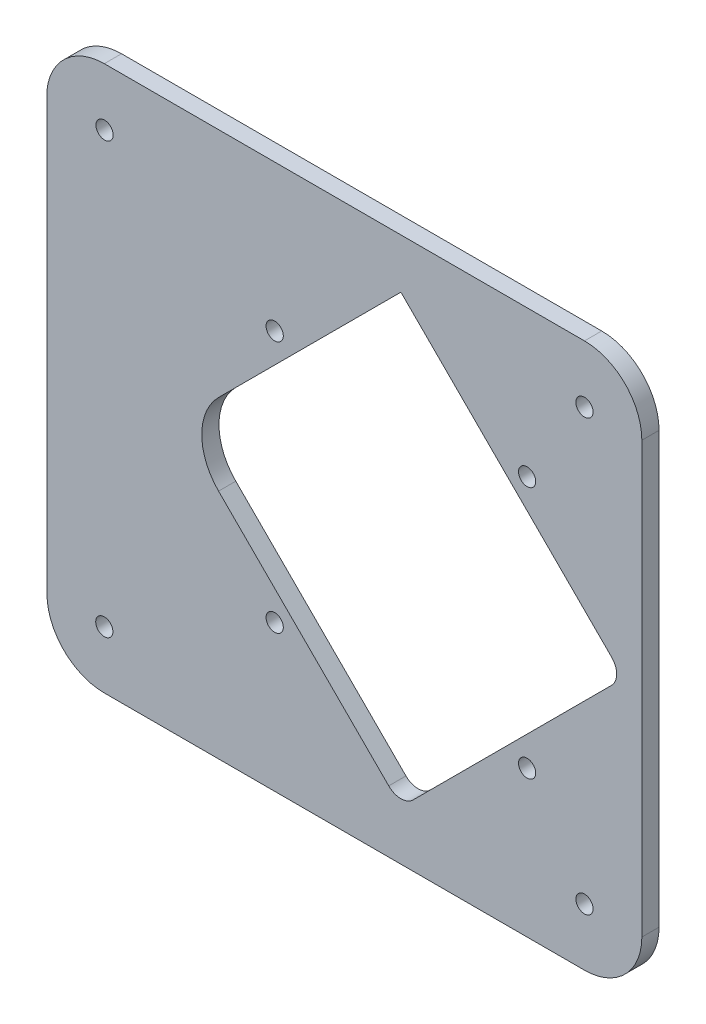
SolidWorks part; units mm, degrees
ref_plane "Front Plane" through (0, 0, 0) normal (0, 0, 1) x (1, 0, 0)
ref_plane "Top Plane" through (0, 0, 0) normal (0, 1, 0) x (1, 0, 0)
ref_plane "Right Plane" through (0, 0, 0) normal (1, 0, 0) x (0, 0, -1)
sketch "Model" plane through (0, 0, 0) normal (0, 0, 1) x (1, 0, 0)
  line L0 (75.7359, 67.6401) -> (82.0642, 73.9684)
  line L3 (117.2673, 85.8158) -> (33.5676, 85.8158)
  line L4 (23.5676, 11.7907) -> (23.5676, 67.2113)
  line L5 (23.5676, 0.8161) -> (23.5676, 11.7907)
  line L6 (23.5676, 67.2113) -> (23.5676, 76.8159)
  line L7 (127.2672, 11.5942) -> (127.2672, 49.316)
  line L8 (127.2672, 49.316) -> (127.2672, 75.8159)
  line L9 (127.2672, 0.8161) -> (127.2672, 11.5942)
  line L10 (33.5676, -9.1838) -> (117.2673, -9.1838)
  line L11 (63.2676, 16.3159) -> (107.2676, 16.3159) construction
  line L12 (107.2676, 60.3158) -> (107.2676, 16.3159) construction
  line L22 (122.0014, 40.4377) -> (89.4636, 72.9755)
  line L23 (87.3887, 1.5824) -> (122.0014, 36.1951)
  line L24 (53.4833, 31.2453) -> (83.1461, 1.5824)
  line L25 (85.2674, 77.1716) -> (82.0642, 73.9684)
  line L26 (89.4636, 72.9755) -> (85.2674, 77.1716)
  line L27 (75.7359, 67.6401) -> (53.3954, 45.2995)
  circle A0 centre (63.2676, 16.3159) radius 1.5
  circle A1 centre (117.2672, 75.8159) radius 1.5
  circle A2 centre (117.2672, 0.8161) radius 1.5
  circle A3 centre (33.61, 75.8159) radius 1.5
  circle A4 centre (33.5676, 0.8161) radius 1.5
  circle A5 centre (107.2676, 16.3159) radius 1.5
  circle A6 centre (63.2676, 60.3159) radius 1.5
  circle A7 centre (107.2676, 60.3158) radius 1.5
  arc A8 (127.2672, 75.8159) -> (117.2673, 85.8158) centre (117.2673, 75.816) ccw
  arc A9 (117.2673, -9.1838) -> (127.2672, 0.8161) centre (117.2672, 0.8161) ccw
  arc A10 (23.5676, 0.8161) -> (33.5676, -9.1838) centre (33.5676, 0.8162) ccw
  arc A11 (33.5676, 85.8158) -> (23.5676, 76.8159) centre (33.6101, 75.7131) ccw
  arc A12 (122.0014, 36.1951) -> (122.0014, 40.4377) centre (119.8801, 38.3164) ccw
  arc A13 (83.1461, 1.5824) -> (87.3887, 1.5824) centre (85.2674, 3.7037) ccw
  arc A14 (53.4833, 45.3874) -> (53.4833, 31.2453) centre (60.5543, 38.3164) ccw
  dimension "D1" = 44
  dimension "D2" = 44
extrude "Boss-Extrude1" add sketch "Model" along normal blind 3 contours A11 L6 L4 L5 A10 L10 A9 L9 L7 L8 A8 L3 A14 L27 L0 L25 L26 L22 A12 L23 A13 L24 A0 A1 A2 region at (123.3439, 81.8925, 0)
